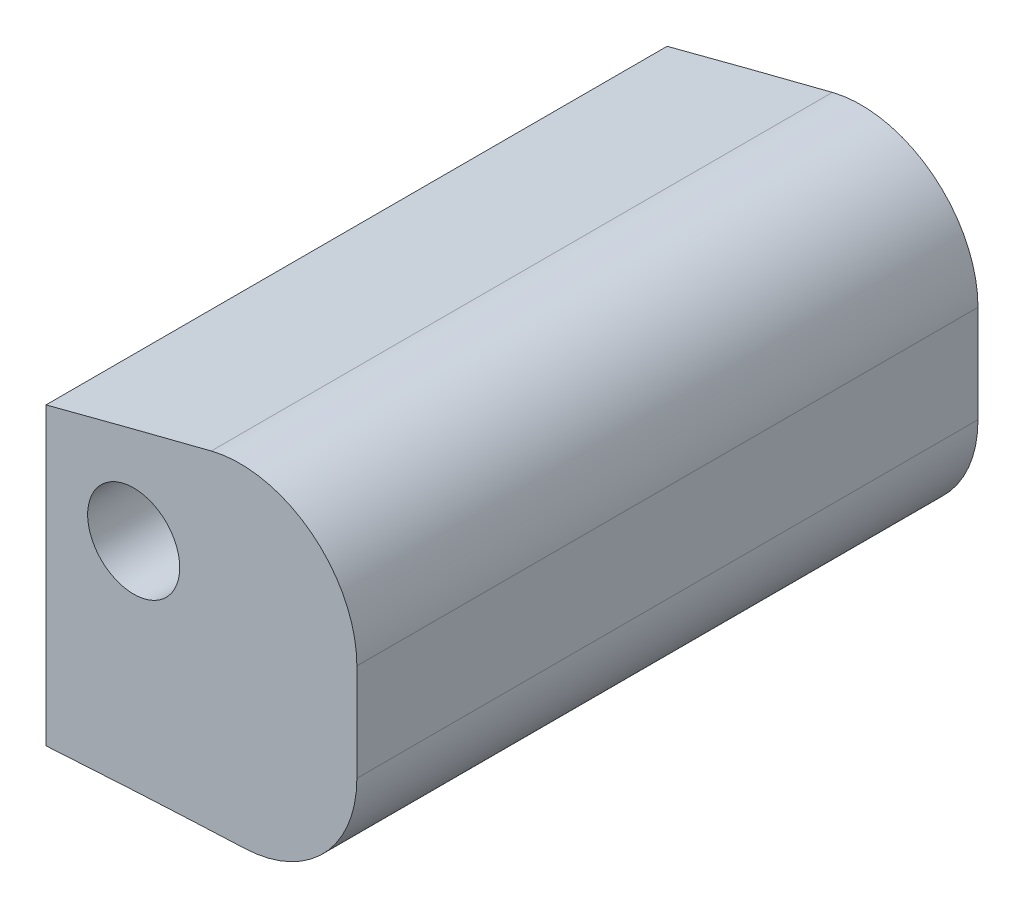
SolidWorks part; units mm, degrees
ref_plane "Front Plane" through (0, 0, 0) normal (0, 0, 1) x (1, 0, 0)
ref_plane "Top Plane" through (0, 0, 0) normal (0, 1, 0) x (1, 0, 0)
ref_plane "Right Plane" through (0, 0, 0) normal (1, 0, 0) x (0, 0, -1)
sketch "Sketch1" plane through (0, 0, 0) normal (0, 0, 1) x (1, 0, 0)
  line L1 (36.0875, 3) -> (36.0875, 7.228)
  circle A3 centre (26.3907, 7.0797) radius 2
  arc A4 (31.2216, -2.0755) -> (36.0875, 3) centre (31.0075, 3) ccw
  arc A5 (36.0875, 7.228) -> (29.7604, 12.1525) centre (31.0075, 7.228) ccw
  spline S0 degree 3 poles (-32.0293, -8.1603) (-27.5943, -7.0527) (-20.0884, -6.5835) (-6.7403, -4.761) (4.8697, -4.0726) (18.4945, -2.7427) (26.2047, -2.2872) (31.2216, -2.0755) knots 0 0 0 0 0.144322 0.237948 0.427123 0.512832 0.672025 0.672025 0.672025 0.672025
  spline S1 degree 3 poles (29.7604, 12.1525) (20.1046, 9.7074) (4.1606, 5.3612) (-17.3533, -1.5993) (-25.5736, -4.86) (-35.7724, -8.5491) (-32.0293, -8.1603) knots 0.330745 0.330745 0.330745 0.330745 0.630725 0.824214 0.940085 1 1 1 1
  dimension "D2" = 4
  dimension "D1" = 63.2509
extrude "Boss-Extrude1" add sketch "Sketch1" along normal blind 26.9875
sketch "Sketch2" plane through (0, 0, 26.9875) normal (0, 0, 1) x (1, 0, 0)
  line L1 (22.5807, 14.1313) -> (-63.7836, 14.1313)
  line L2 (22.5807, 14.1313) -> (22.5807, -20.6835)
  line L3 (22.5807, -20.6835) -> (-63.7836, -20.6835)
  line L4 (-63.7836, 14.1313) -> (-63.7836, -20.6835)
  circle A1 centre (26.3907, 7.0797) radius 2 construction
  dimension "D1" = 3.81
extrude "Cut-Extrude1" cut sketch "Sketch2" against normal through all
